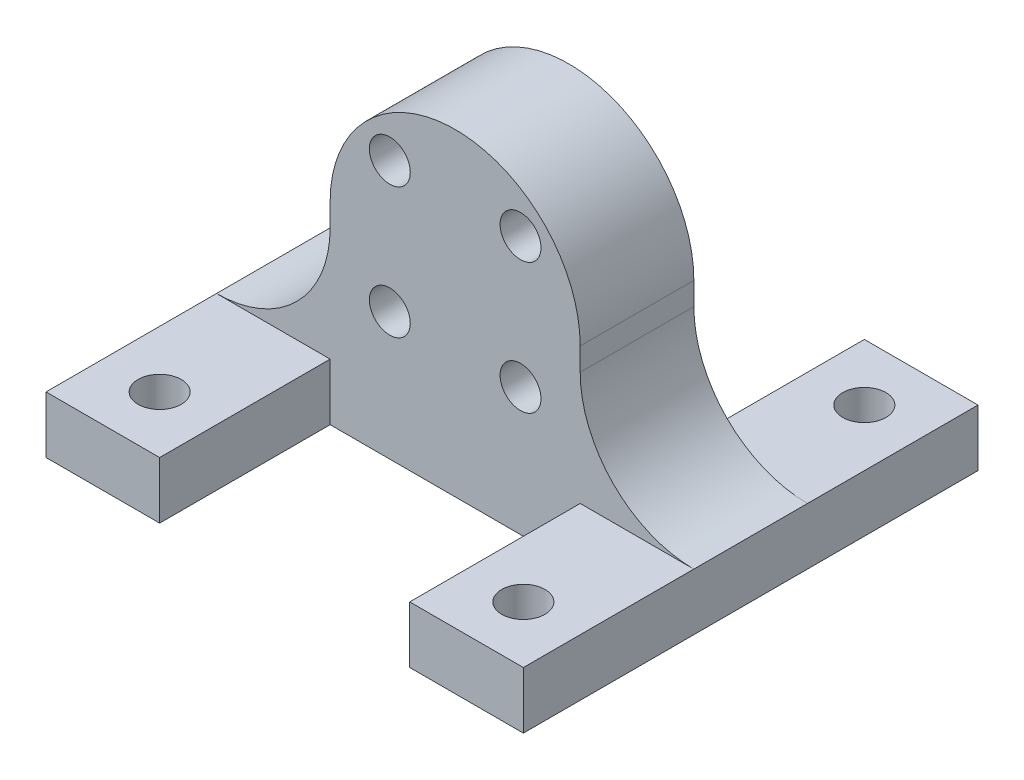
SolidWorks part; units mm, degrees
ref_plane "Front Plane" through (0, 0, 0) normal (0, 0, 1) x (1, 0, 0)
ref_plane "Top Plane" through (0, 0, 0) normal (0, 1, 0) x (1, 0, 0)
ref_plane "Right Plane" through (0, 0, 0) normal (1, 0, 0) x (0, 0, -1)
sketch "Sketch1" plane through (0, 0, 0) normal (0, 0, 1) x (1, 0, 0)
  line L1 (-5.75, 5.75) -> (5.75, 5.75) construction
  line L2 (-5.75, 5.75) -> (-5.75, -5.75) construction
  line L3 (-5.75, -5.75) -> (5.75, -5.75) construction
  line L4 (5.75, 5.75) -> (5.75, -5.75) construction
  line L5 (-5.75, 5.75) -> (5.75, -5.75) construction
  line L6 (-5.75, -5.75) -> (5.75, 5.75) construction
  circle A0 centre (-5.75, 5.75) radius 1.8
  circle A1 centre (5.75, 5.75) radius 1.8
  circle A2 centre (5.75, -5.75) radius 1.8
  circle A3 centre (-5.75, -5.75) radius 1.8
  circle A4 centre (0, 0) radius 11
  point P0 (0, 0)
  dimension "D1" = 3.6
  dimension "D3" = 22
  dimension "D2" = 11.5
extrude "Boss-Extrude1" add sketch "Sketch1" along normal blind 10
sketch "Sketch2" plane through (0, 0, 0) normal (0, 0, -1) x (-1, 0, 0)
  line L0 (-11, 0) -> (-11, -12)
  line L1 (-11, -12) -> (11, -12)
  line L2 (11, -12) -> (11, 0)
  arc A0 (-11, 0) -> (11, 0) centre (0, 0) ccw
  circle A1 centre (0, 0) radius 11 construction
  point P6 (0, -11)
  circle M1 centre (0, 0) radius 11
  dimension "D1" = 1
extrude "Boss-Extrude2" add sketch "Sketch2" against normal up to surface (10 mm away) contours L0 L1 M1 | L1 L2 M1 region at (0, -11.2506, 0) up to face at (7.55, -5.75, 10)
sketch "Sketch3" plane through (0, -12, 0) normal (0, -1, 0) x (1, 0, 0)
  line L0 (0, 0) -> (0, 10) construction
  line L1 (11, 10) -> (-11, 10) construction
  line L7 (11, 10) -> (11, 0) construction
  line L8 (-11, 10) -> (-11, 0) construction
  line L9 (-11, 10) -> (-11, 25)
  line L10 (-11, 25) -> (-21, 25)
  line L11 (-21, 25) -> (-21, -15)
  line L12 (-21, -15) -> (-11, -15)
  line L13 (-11, -15) -> (-11, 0)
  line L14 (-11, 0) -> (11, 0)
  line L15 (11, 0) -> (11, -15)
  line L16 (11, -15) -> (21, -15)
  line L17 (21, -15) -> (21, 25)
  line L18 (21, 25) -> (11, 25)
  line L19 (11, 25) -> (11, 10)
  line L21 (11, 10) -> (-11, 10)
  line L22 (0, 5) -> (6.1746, 5) construction
  line L23 (16, -15) -> (16, -10) construction
  circle A4 centre (16, -10) radius 1.9
  circle A5 centre (16, 20) radius 1.9
  circle A6 centre (-16, 20) radius 1.9
  circle A7 centre (-16, -10) radius 1.9
  point P5 (0, 5)
  dimension "D4" = 5
  dimension "D5" = 3.8
  dimension "D1" = 10
  dimension "D2" = 10
  dimension "D3" = 15
extrude "Boss-Extrude3" add sketch "Sketch3" along normal blind 5
fillet "Fillet2" radius 10 2 edges at (11, -12, 5) (-11, -12, 5)
